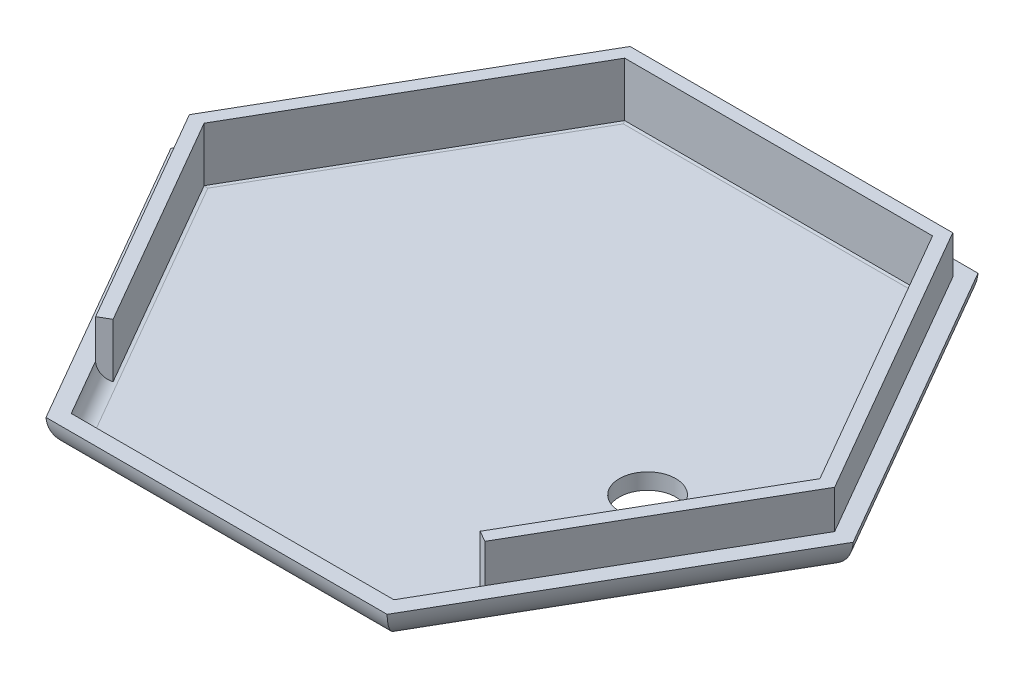
SolidWorks part; units mm, degrees
ref_plane "Front Plane" through (0, 0, 0) normal (0, 0, 1) x (1, 0, 0)
ref_plane "Top Plane" through (0, 0, 0) normal (0, 1, 0) x (1, 0, 0)
ref_plane "Right Plane" through (0, 0, 0) normal (1, 0, 0) x (0, 0, -1)
sketch "Sketch1" plane through (0, 0, 0) normal (0, 1, 0) x (1, 0, 0)
  line L0 (-15.875, 4.4188) -> (0, -4.7467)
  line L1 (-15.875, 4.4188) -> (-0.381, -23.7374)
  line L2 (-0.381, -23.7374) -> (15.875, 4.4188)
  line L3 (15.875, 4.4188) -> (-15.875, 4.4188)
  line L4 (0, -4.7467) -> (-5.9228, -4.7467)
  line L5 (-16.584, -24.2454) -> (-15.0346, -23.7374) construction
  line L6 (15.42, -24.2454) -> (13.8706, -23.7374) construction
  line L7 (-34.4191, 3.4708) -> (-17.5005, -25.8329)
  line L8 (-17.5005, -25.8329) -> (16.3366, -25.8329)
  line L9 (16.3366, -25.8329) -> (33.2551, 3.4708)
  line L10 (15.42, -24.2454) -> (31.422, 3.4708)
  line L11 (-23.3776, -8.5762) -> (-8.643, 16.9449)
  line L12 (-8.643, 16.9449) -> (8.643, 16.9449)
  line L13 (0, -4.7467) -> (0, 0.7198) construction
  line L14 (22.5136, -8.7673) -> (13.8706, -23.7374)
  line L15 (8.643, 16.9449) -> (22.5136, -8.7673)
  line L16 (-15.0346, -23.7374) -> (-23.3776, -8.5762)
  line L17 (13.8706, -23.7374) -> (-15.0346, -23.7374)
  line L18 (0, -4.7467) -> (0, 11.9411)
  line L19 (0, -4.7467) -> (14.4521, -13.0906)
  line L20 (0, -4.7467) -> (-14.4521, -13.0906)
  line L21 (33.2551, 3.4708) -> (16.3366, 32.7746)
  line L22 (16.3366, 32.7746) -> (-17.5005, 32.7746)
  line L23 (-17.5005, 32.7746) -> (-34.4191, 3.4708)
  line L32 (31.422, 3.4708) -> (15.42, 31.1871)
  line L33 (15.42, 31.1871) -> (-16.584, 31.1871)
  line L34 (-16.584, 31.1871) -> (-32.586, 3.4708)
  line L35 (-32.586, 3.4708) -> (-16.584, -24.2454)
  line L36 (-16.584, -24.2454) -> (15.42, -24.2454)
  circle A0 centre (0, -4.7467) radius 9.4895 construction
  circle A1 centre (-6.096, 12.5253) radius 1.27
  circle A2 centre (-10.16, -18.9707) radius 1.27
  circle A3 centre (10.16, -18.9707) radius 1.27
  circle A4 centre (6.096, 12.5253) radius 1.27
  circle A5 centre (-0.582, 3.4708) radius 32.004 construction
  point P1 (18.7617, 27.5336)
  point P7 (35.4695, -1.4053)
  point P8 (-35.4741, -1.3973)
  point P9 (-18.7617, 27.5336)
  point P17 (0, 16.9449)
  point P23 (0, 0)
  point P26 (0, 0)
  point P28 (0, 0)
  point P42 (0, -6.4857)
  point P43 (35.9745, -19.0866)
  point P44 (-35.9745, -19.0866)
  dimension "D16" = 2.54
  dimension "D19" = 2.54
  dimension "D1" = 30
  dimension "D2" = 31.75
  dimension "D3" = 0.508
  dimension "D4" = 0.582
  dimension "D5" = 60
  dimension "D6" = 1.5875
  dimension "D7" = 22.5136
  dimension "D8" = 4.0206
  dimension "D9" = 21.6916
  dimension "D10" = 8.643
  dimension "D11" = 28.9052
  dimension "D13" = 16.6878
  dimension "D14" = 14.4521
  dimension "D15" = 8.3439
  dimension "D17" = 6.096
  dimension "D18" = 17.272
  dimension "D21" = 14.224
  dimension "D23" = 32.004
  dimension "D26" = 15.875
  dimension "D27" = 9.1654
extrude "Boss-Extrude1" add sketch "Sketch1" along normal blind 1.5875 contours L20 L0 L1 | L19 L20 L1 L2 | L18 L19 L2 L3 | L0 L18 L3 | L15 L12 L11 L3 A1 A4 | L17 L14 L15 L2 A3 | A3 | A2 | L17 L1 L11 L16 A2 | A1 | A4 | L15 L14 | L12 | L11 L16 | L17 | L22 L23 L7 L8 L9 L21 L36 L35 L34 L33 L32 L10 | L3 L15 L2 region at (-5.2917, 0, -1.3636) region at (-8.0316, 0, 3.2734) region at (-0.1345, 0, -9.9962) region at (-13.1611, 0, 12.4796) region at (6.6083, 0, 0.9313) region at (-0.1899, 0, 12.6318) region at (12.4195, 0, 12.6389) region at (15.635, 0, -4.2771) region at (-25.1845, 0, -17.6751) region at (-0.582, 0, 24.1608) region at (-6.096, 0, -12.5253) region at (-10.16, 0, 18.9707) region at (10.16, 0, 18.9707) region at (6.096, 0, -12.5253)
sketch "Sketch2" plane through (0, 1.5875, 0) normal (0, 1, 0) x (1, 0, 0)
  line L0 (-17.5005, 32.7746) -> (-34.4191, 3.4708)
  line L1 (-34.4191, 3.4708) -> (-17.5005, -25.8329)
  line L2 (-17.5005, -25.8329) -> (16.3366, -25.8329)
  line L3 (16.3366, -25.8329) -> (33.2551, 3.4708)
  line L4 (33.2551, 3.4708) -> (16.3366, 32.7746)
  line L5 (16.3366, 32.7746) -> (-17.5005, 32.7746)
  line L6 (-16.584, 31.1871) -> (15.42, 31.1871)
  line L7 (15.42, 31.1871) -> (31.422, 3.4708)
  line L8 (31.422, 3.4708) -> (15.42, -24.2454)
  line L9 (15.42, -24.2454) -> (-16.584, -24.2454)
  line L10 (-16.584, -24.2454) -> (-32.586, 3.4708)
  line L11 (-32.586, 3.4708) -> (-16.584, 31.1871)
  point P11 (-0.0029, -6.4929)
  point P13 (37.2102, -18.7507)
  point P14 (-37.2102, -18.7507)
  point P16 (38.1175, -6.4857)
extrude "Boss-Extrude2" add sketch "Sketch2" along normal blind 1.5875 contours L4 | L4 | L4 L5 L0 L1 L2 L3 L10 L11 L6 L7 L8 L9 region at (-0.582, 1.5875, -31.8794)
fillet "Fillet2" radius 1.5875 6 edges at (23.421, 1.5875, -17.329) (23.421, 1.5875, 10.3873) (-24.585, 1.5875, -17.329) (-0.582, 1.5875, 24.2454) (-24.585, 1.5875, 10.3873) (-0.582, 1.5875, -31.1871)
fillet "Fillet3" radius 3.302 6 edges at (-0.582, 0, 25.8329) (-25.9598, 0, 11.181) (-25.9598, 0, -18.1227) (-0.582, 0, -32.7746) (24.7958, 0, 11.181) (24.7958, 0, -18.1227)
sketch "Sketch4" plane through (0, 3.175, 0) normal (0, 1, 0) x (1, 0, 0)
  line L0 (-32.586, 3.4708) -> (-16.584, 31.1871)
  line L1 (-16.584, 31.1871) -> (15.42, 31.1871)
  line L2 (15.42, 31.1871) -> (31.422, 3.4708)
  line L3 (31.422, 3.4708) -> (18.722, -18.5262)
  line L4 (31.422, 3.4708) -> (15.42, -24.2454) construction
  line L5 (-32.586, 3.4708) -> (-19.886, -18.5262)
  line L6 (-16.584, -24.2454) -> (-32.586, 3.4708) construction
  line L7 (-31.1195, 3.4708) -> (-18.7861, -17.8912)
  line L8 (-31.1195, 3.4708) -> (-15.8507, 29.9171)
  line L9 (-15.8507, 29.9171) -> (14.6868, 29.9171)
  line L10 (14.6868, 29.9171) -> (29.9555, 3.4708)
  line L11 (29.9555, 3.4708) -> (17.6222, -17.8912)
  line L12 (-18.7861, -17.8912) -> (-19.886, -18.5262)
  line L13 (18.722, -18.5262) -> (17.6222, -17.8912)
  dimension "D1" = 25.4
  dimension "D2" = 25.4
  dimension "D3" = 1.27
extrude "Boss-Extrude3" add sketch "Sketch4" along normal blind 3.81 and the other way up to next
sketch "Sketch5" plane through (0, 1.5875, 0) normal (0, 1, 0) x (1, 0, 0)
  circle A0 centre (17.4017, -1.0651) radius 2.7979
extrude "Cut-Extrude1" cut sketch "Sketch5" against normal blind 3.81
